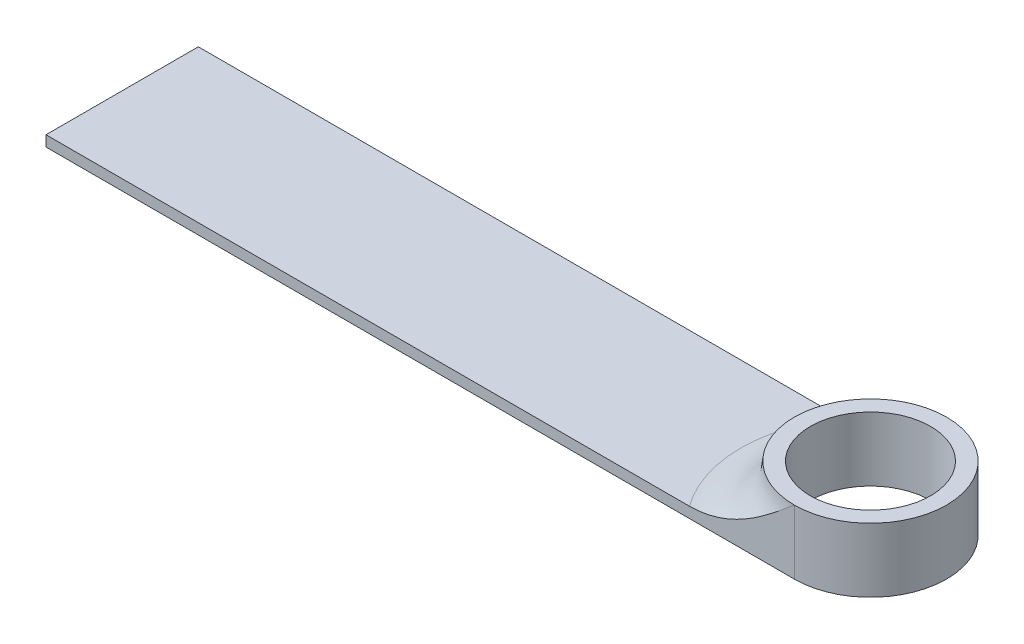
SolidWorks part; units mm, degrees
ref_plane "Front Plane" through (0, 0, 0) normal (0, 0, 1) x (1, 0, 0)
ref_plane "Top Plane" through (0, 0, 0) normal (0, 1, 0) x (1, 0, 0)
ref_plane "Right Plane" through (0, 0, 0) normal (1, 0, 0) x (0, 0, -1)
sketch "Sketch1" plane through (0, 0, 0) normal (0, 1, 0) x (1, 0, 0)
  line L0 (0, -14.25) -> (-140, -14.25)
  line L1 (0, 14.25) -> (-140, 14.25)
  line L2 (-140, 14.25) -> (-140, -14.25)
  arc A0 (0, 14.25) -> (0, -14.25) centre (0, 0) cw
  circle A1 centre (0, 0) radius 11.25
  dimension "D1" = 22.5
  dimension "D2" = 3
  dimension "D3" = 140
extrude "Boss-Extrude1" add sketch "Sketch1" along normal blind 2
sketch "Sketch2" plane through (0, 2, 0) normal (0, 1, 0) x (1, 0, 0)
  circle A0 centre (0, 0) radius 11.25
extrude "Extrude-Thin1" add sketch "Sketch2" along normal blind 10 thin thin type one direction wall 3
fillet "Fillet1" radius 10 1 edges at (-14.25, 2, 0)
